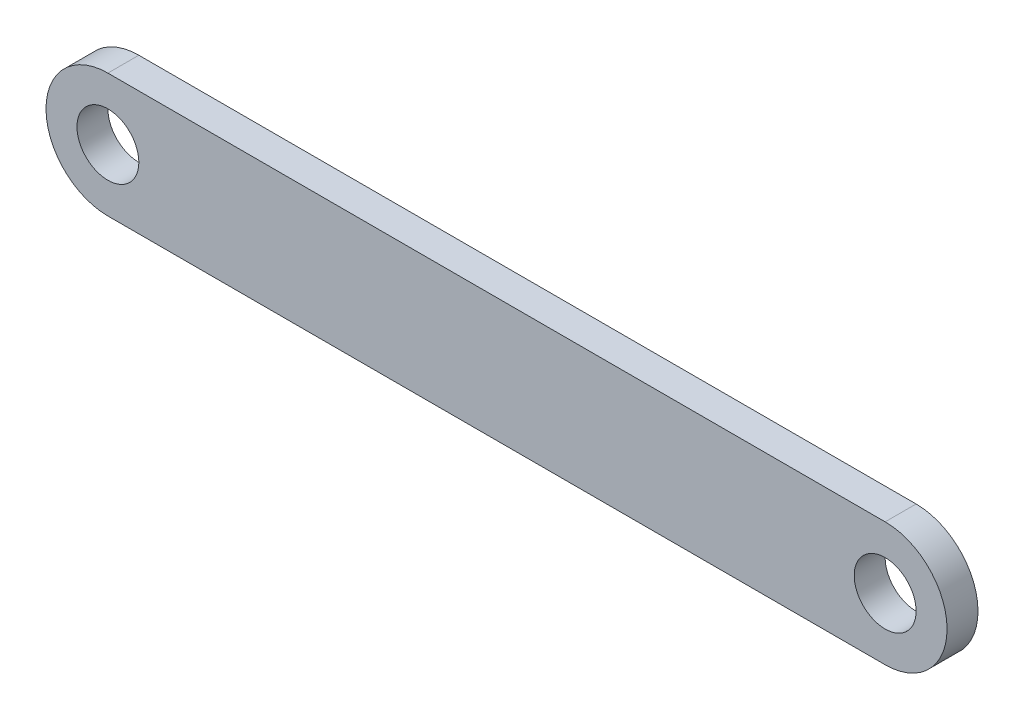
SolidWorks part; units mm, degrees
ref_plane "Спереди" through (0, 0, 0) normal (0, 0, 1) x (1, 0, 0)
ref_plane "Сверху" through (0, 0, 0) normal (0, 1, 0) x (1, 0, 0)
ref_plane "Справа" through (0, 0, 0) normal (1, 0, 0) x (0, 0, -1)
sketch "Sketch1" plane through (0, 0, 0) normal (0, 0, 1) x (1, 0, 0)
  line L0 (0, 0) -> (-25.1163, 0)
  line L1 (-25.1163, 2) -> (0, 2)
  line L2 (-25.1163, -2) -> (0, -2)
  circle A0 centre (0, 0) radius 1
  circle A1 centre (0, 0) radius 2
  circle A2 centre (-25.1163, 0) radius 1
  circle A3 centre (-25.1163, 0) radius 2
extrude "Extrude1" add sketch "Sketch1" along normal blind 1 contours A3 L2 A1 L0 | A3 L0 A1 L1 | A3 A2 | A1 A0 region at (-12.5582, 1.0216, 0) region at (-23.7421, -1.3742, 0) region at (-12.5581, -1.0216, 0) region at (-1.3742, 1.3742, 0)
